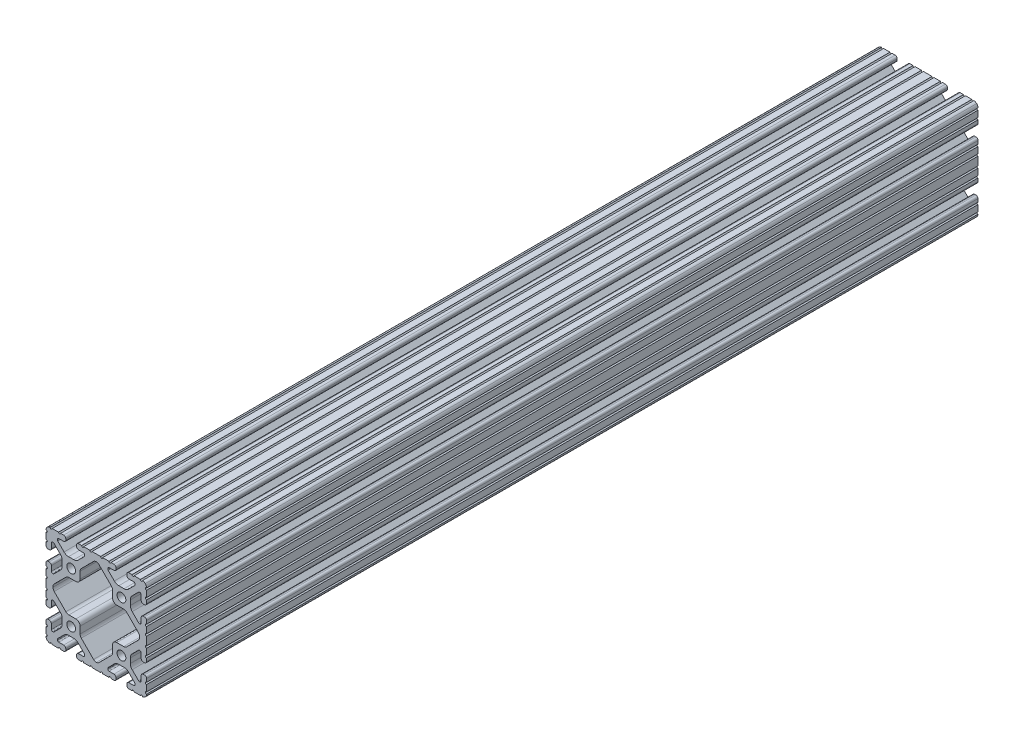
SolidWorks part; units mm, degrees
ref_plane "Front Plane" through (0, 0, 0) normal (0, 0, 1) x (1, 0, 0)
ref_plane "Top Plane" through (0, 0, 0) normal (0, 1, 0) x (1, 0, 0)
ref_plane "Right Plane" through (0, 0, 0) normal (1, 0, 0) x (0, 0, -1)
sketch "Sketch1" plane through (0, 0, 0) normal (0, 0, 1) x (1, 0, 0)
  line L0 (0, 38.1) -> (0, -38.1) construction
  line L1 (-38.1, -38.1) -> (38.1, -38.1) construction
  line L2 (-38.1, -38.1) -> (-38.1, 38.1) construction
  line L3 (-38.1, 38.1) -> (38.1, 38.1) construction
  line L4 (38.1, -38.1) -> (38.1, 38.1) construction
  line L5 (0, 38.1) -> (0, -38.1) construction
  line L6 (-38.1, 0) -> (38.1, 0) construction
  line L7 (-19.05, 19.05) -> (19.05, 19.05) construction
  line L8 (-19.05, 19.05) -> (-19.05, -19.05) construction
  line L9 (-19.05, -19.05) -> (19.05, -19.05) construction
  line L10 (19.05, 19.05) -> (19.05, -19.05) construction
  line L11 (-23.114, 38.1) -> (-23.114, -38.1) construction
  line L12 (-23.114, -38.1) -> (-14.986, 38.1) construction
  line L13 (-14.986, 38.1) -> (-14.986, -38.1) construction
  circle A0 centre (19.05, 19.05) radius 3.3274
  point P0 (0, 0)
  point P9 (0, 0)
  point P12 (-19.05, 0)
  line B0 (-11.3637, -22.8433) -> (-2.0515, -32.1555)
  line B1 (-12.2936, -15.4686) -> (-12.2936, -20.5983)
  line B2 (-20.769, -12.2936) -> (-15.4686, -12.2936)
  line B3 (-31.9021, -2.4756) -> (-23.0141, -11.3637)
  line B4 (-23.0141, 11.3637) -> (-31.9021, 2.4756)
  line B5 (-15.4686, 12.2936) -> (-20.769, 12.2936)
  line B6 (-12.2936, 20.5983) -> (-12.2936, 15.4686)
  line B7 (-2.0515, 32.1555) -> (-11.3637, 22.8433)
  line B8 (11.3637, 22.8433) -> (2.0515, 32.1555)
  line B9 (12.2936, 15.4686) -> (12.2936, 20.5983)
  line B10 (20.769, 12.2936) -> (15.4686, 12.2936)
  line B11 (31.9021, 2.4756) -> (23.0141, 11.3637)
  line B12 (23.0141, -11.3637) -> (31.9021, -2.4756)
  line B13 (15.4686, -12.2936) -> (20.769, -12.2936)
  line B14 (12.2936, -20.5983) -> (12.2936, -15.4686)
  line B15 (2.0515, -32.1555) -> (11.3637, -22.8433)
  line B16 (-4.7773, 38.1) -> (-9.6053, 38.1)
  line B17 (-11.1289, 38.1) -> (-13.4112, 38.1)
  line B18 (-14.986, 36.5252) -> (-14.986, 35.6108)
  line B19 (-13.4112, 34.036) -> (-9.652, 34.036)
  line B20 (-8.763, 33.147) -> (-8.763, 32.4935)
  line B21 (-9.0234, 31.8649) -> (-13.6907, 27.1976)
  line B22 (-17.0493, 25.8064) -> (-21.0507, 25.8064)
  line B23 (-24.4093, 27.1976) -> (-29.1002, 31.8885)
  line B24 (-29.337, 32.7207) -> (-29.337, 33.147)
  line B25 (-28.448, 34.036) -> (-24.6888, 34.036)
  line B26 (-23.114, 35.6108) -> (-23.114, 36.5252)
  line B27 (-24.6888, 38.1) -> (-27.0772, 38.1)
  line B28 (-28.6011, 38.1) -> (-33.4288, 38.1)
  line B29 (-38.1, 33.373) -> (-38.1, 28.5453)
  line B30 (-38.1, 27.0238) -> (-38.1, 24.6302)
  line B31 (-36.5252, 23.0554) -> (-35.6108, 23.0554)
  line B32 (-34.036, 24.6302) -> (-34.036, 28.448)
  line B33 (-33.147, 29.337) -> (-32.6643, 29.337)
  line B34 (-32.0357, 29.0766) -> (-27.1976, 24.2385)
  line B35 (-25.8064, 20.8799) -> (-25.8064, 17.2201)
  line B36 (-27.1976, 13.8615) -> (-31.9489, 9.1101)
  line B37 (-32.7869, 8.763) -> (-33.0603, 8.763)
  line B38 (-34.036, 9.7387) -> (-34.036, 13.4698)
  line B39 (-35.6108, 15.0446) -> (-36.5252, 15.0446)
  line B40 (-38.1, 13.4698) -> (-38.1, 11.075)
  line B41 (-38.1, 9.552) -> (-38.1, 4.7238)
  line B42 (-38.1, 3.2007) -> (-38.1, -3.2007)
  line B43 (-38.1, -4.7238) -> (-38.1, -9.552)
  line B44 (-38.1, -11.075) -> (-38.1, -13.4698)
  line B45 (-36.5252, -15.0446) -> (-35.6108, -15.0446)
  line B46 (-34.036, -13.4698) -> (-34.036, -9.7387)
  line B47 (-33.0603, -8.763) -> (-32.7869, -8.763)
  line B48 (-31.9489, -9.1101) -> (-27.1976, -13.8615)
  line B49 (-25.8064, -17.2201) -> (-25.8064, -20.8799)
  line B50 (-27.1976, -24.2385) -> (-32.0357, -29.0766)
  line B51 (-32.6643, -29.337) -> (-33.147, -29.337)
  line B52 (-34.036, -28.448) -> (-34.036, -24.6302)
  line B53 (-35.6108, -23.0554) -> (-36.5252, -23.0554)
  line B54 (-38.1, -24.6302) -> (-38.1, -27.0238)
  line B55 (-38.1, -28.5453) -> (-38.1, -33.373)
  line B56 (-33.4288, -38.1) -> (-28.6011, -38.1)
  line B57 (-27.0772, -38.1) -> (-24.6888, -38.1)
  line B58 (-23.114, -36.5252) -> (-23.114, -35.6108)
  line B59 (-24.6888, -34.036) -> (-28.448, -34.036)
  line B60 (-29.337, -33.147) -> (-29.337, -32.7207)
  line B61 (-29.1002, -31.8885) -> (-24.4093, -27.1976)
  line B62 (-21.0507, -25.8064) -> (-17.0493, -25.8064)
  line B63 (-13.6907, -27.1976) -> (-9.0234, -31.8649)
  line B64 (-8.763, -32.4935) -> (-8.763, -33.147)
  line B65 (-9.652, -34.036) -> (-13.4112, -34.036)
  line B66 (-14.986, -35.6108) -> (-14.986, -36.5252)
  line B67 (-13.4112, -38.1) -> (-11.1289, -38.1)
  line B68 (-9.6053, -38.1) -> (-4.7773, -38.1)
  line B69 (-3.2537, -38.1) -> (3.2537, -38.1)
  line B70 (4.7773, -38.1) -> (9.6053, -38.1)
  line B71 (11.1289, -38.1) -> (13.4112, -38.1)
  line B72 (14.986, -36.5252) -> (14.986, -35.6108)
  line B73 (13.4112, -34.036) -> (9.652, -34.036)
  line B74 (8.763, -33.147) -> (8.763, -32.4935)
  line B75 (9.0234, -31.8649) -> (13.6907, -27.1976)
  line B76 (17.0493, -25.8064) -> (21.0507, -25.8064)
  line B77 (24.4093, -27.1976) -> (29.1002, -31.8885)
  line B78 (29.337, -32.7207) -> (29.337, -33.147)
  line B79 (28.448, -34.036) -> (24.6888, -34.036)
  line B80 (23.114, -35.6108) -> (23.114, -36.5252)
  line B81 (24.6888, -38.1) -> (27.0772, -38.1)
  line B82 (28.6011, -38.1) -> (33.4288, -38.1)
  line B83 (38.1, -33.373) -> (38.1, -28.5453)
  line B84 (38.1, -27.0238) -> (38.1, -24.6302)
  line B85 (36.5252, -23.0554) -> (35.6108, -23.0554)
  line B86 (34.036, -24.6302) -> (34.036, -28.448)
  line B87 (33.147, -29.337) -> (32.6643, -29.337)
  line B88 (32.0357, -29.0766) -> (27.1976, -24.2385)
  line B89 (25.8064, -20.8799) -> (25.8064, -17.2201)
  line B90 (27.1976, -13.8615) -> (31.9489, -9.1101)
  line B91 (32.7869, -8.763) -> (33.0603, -8.763)
  line B92 (34.036, -9.7387) -> (34.036, -13.4698)
  line B93 (35.6108, -15.0446) -> (36.5252, -15.0446)
  line B94 (38.1, -13.4698) -> (38.1, -11.075)
  line B95 (38.1, -9.552) -> (38.1, -4.7238)
  line B96 (38.1, -3.2007) -> (38.1, 3.2007)
  line B97 (38.1, 4.7238) -> (38.1, 9.552)
  line B98 (38.1, 11.075) -> (38.1, 13.4698)
  line B99 (36.5252, 15.0446) -> (35.6108, 15.0446)
  line B100 (34.036, 13.4698) -> (34.036, 9.7387)
  line B101 (33.0603, 8.763) -> (32.7869, 8.763)
  line B102 (31.9489, 9.1101) -> (27.1976, 13.8615)
  line B103 (25.8064, 17.2201) -> (25.8064, 20.8799)
  line B104 (27.1976, 24.2385) -> (32.0357, 29.0766)
  line B105 (32.6643, 29.337) -> (33.147, 29.337)
  line B106 (34.036, 28.448) -> (34.036, 24.6302)
  line B107 (35.6108, 23.0554) -> (36.5252, 23.0554)
  line B108 (38.1, 24.6302) -> (38.1, 27.0238)
  line B109 (38.1, 28.5453) -> (38.1, 33.373)
  line B110 (33.4288, 38.1) -> (28.6011, 38.1)
  line B111 (27.0772, 38.1) -> (24.6888, 38.1)
  line B112 (23.114, 36.5252) -> (23.114, 35.6108)
  line B113 (24.6888, 34.036) -> (28.448, 34.036)
  line B114 (29.337, 33.147) -> (29.337, 32.7207)
  line B115 (29.1002, 31.8885) -> (24.4093, 27.1976)
  line B116 (21.0507, 25.8064) -> (17.0493, 25.8064)
  line B117 (13.6907, 27.1976) -> (9.0234, 31.8649)
  line B118 (8.763, 32.4935) -> (8.763, 33.147)
  line B119 (9.652, 34.036) -> (13.4112, 34.036)
  line B120 (14.986, 35.6108) -> (14.986, 36.5252)
  line B121 (13.4112, 38.1) -> (11.1289, 38.1)
  line B122 (9.6053, 38.1) -> (4.7773, 38.1)
  line B123 (3.2537, 38.1) -> (-3.2537, 38.1)
  circle B124 centre (-19.05, 19.05) radius 3.3274
  circle B125 centre (-19.05, -19.05) radius 3.3274
  circle B126 centre (19.05, -19.05) radius 3.3274
  circle B127 centre (19.05, 19.05) radius 3.3274
  arc B128 (0, -33.011) -> (2.0515, -32.1555) centre (-0.0139, -30.09) ccw
  arc B129 (-2.0515, -32.1555) -> (0, -33.011) centre (0.0139, -30.09) ccw
  arc B130 (-12.2936, -20.5983) -> (-11.3637, -22.8433) centre (-9.1186, -20.5983) ccw
  arc B131 (-12.2936, -15.4686) -> (-15.4686, -12.2936) centre (-15.4686, -15.4686) ccw
  arc B132 (-23.0141, -11.3637) -> (-20.769, -12.2936) centre (-20.769, -9.1186) ccw
  arc B133 (-32.7287, 0) -> (-31.9021, -2.4756) centre (-29.8367, -0.4102) ccw
  arc B134 (-31.9021, 2.4756) -> (-32.7287, 0) centre (-29.8367, 0.4102) ccw
  arc B135 (-20.769, 12.2936) -> (-23.0141, 11.3637) centre (-20.769, 9.1186) ccw
  arc B136 (-15.4686, 12.2936) -> (-12.2936, 15.4686) centre (-15.4686, 15.4686) ccw
  arc B137 (-11.3637, 22.8433) -> (-12.2936, 20.5983) centre (-9.1186, 20.5983) ccw
  arc B138 (0, 33.011) -> (-2.0515, 32.1555) centre (0.0139, 30.09) ccw
  arc B139 (2.0515, 32.1555) -> (0, 33.011) centre (-0.0139, 30.09) ccw
  arc B140 (12.2936, 20.5983) -> (11.3637, 22.8433) centre (9.1186, 20.5983) ccw
  arc B141 (12.2936, 15.4686) -> (15.4686, 12.2936) centre (15.4686, 15.4686) ccw
  arc B142 (23.0141, 11.3637) -> (20.769, 12.2936) centre (20.769, 9.1186) ccw
  arc B143 (32.7287, 0) -> (31.9021, 2.4756) centre (29.8367, 0.4102) ccw
  arc B144 (31.9021, -2.4756) -> (32.7287, 0) centre (29.8367, -0.4102) ccw
  arc B145 (20.769, -12.2936) -> (23.0141, -11.3637) centre (20.769, -9.1186) ccw
  arc B146 (15.4686, -12.2936) -> (12.2936, -15.4686) centre (15.4686, -15.4686) ccw
  arc B147 (11.3637, -22.8433) -> (12.2936, -20.5983) centre (9.1186, -20.5983) ccw
  arc B148 (-4.7773, 38.1) -> (-3.2537, 38.1) centre (-4.0155, 38.0824) ccw
  arc B149 (-11.1289, 38.1) -> (-9.6053, 38.1) centre (-10.3671, 38.0824) ccw
  arc B150 (-13.4112, 38.1) -> (-14.986, 36.5252) centre (-13.4112, 36.5252) ccw
  arc B151 (-14.986, 35.6108) -> (-13.4112, 34.036) centre (-13.4112, 35.6108) ccw
  arc B152 (-8.763, 33.147) -> (-9.652, 34.036) centre (-9.652, 33.147) ccw
  arc B153 (-9.0234, 31.8649) -> (-8.763, 32.4935) centre (-9.652, 32.4935) ccw
  arc B154 (-17.0493, 25.8064) -> (-13.6907, 27.1976) centre (-17.0493, 30.5562) ccw
  arc B155 (-24.4093, 27.1976) -> (-21.0507, 25.8064) centre (-21.0507, 30.5562) ccw
  arc B156 (-29.337, 32.7207) -> (-29.1002, 31.8885) centre (-28.4716, 32.5172) ccw
  arc B157 (-28.448, 34.036) -> (-29.337, 33.147) centre (-28.448, 33.147) ccw
  arc B158 (-24.6888, 34.036) -> (-23.114, 35.6108) centre (-24.6888, 35.6108) ccw
  arc B159 (-23.114, 36.5252) -> (-24.6888, 38.1) centre (-24.6888, 36.5252) ccw
  arc B160 (-28.6011, 38.1) -> (-27.0772, 38.1) centre (-27.8392, 38.0824) ccw
  arc B161 (-34.9527, 38.1) -> (-33.4288, 38.1) centre (-34.1907, 38.0824) ccw
  arc B162 (-34.9527, 38.1) -> (-37.0861, 37.1826) centre (-34.8521, 34.9266) ccw
  arc B163 (-37.0861, 37.1826) -> (-38.1, 34.8455) centre (-34.925, 34.8566) ccw
  arc B164 (-38.1, 33.373) -> (-38.1, 34.8455) centre (-37.9035, 34.1092) ccw
  arc B165 (-38.1, 27.0238) -> (-38.1, 28.5453) centre (-37.9035, 27.7845) ccw
  arc B166 (-38.1, 24.6302) -> (-36.5252, 23.0554) centre (-36.5252, 24.6302) ccw
  arc B167 (-35.6108, 23.0554) -> (-34.036, 24.6302) centre (-35.6108, 24.6302) ccw
  arc B168 (-33.147, 29.337) -> (-34.036, 28.448) centre (-33.147, 28.448) ccw
  arc B169 (-32.0357, 29.0766) -> (-32.6643, 29.337) centre (-32.6643, 28.448) ccw
  arc B170 (-25.8064, 20.8799) -> (-27.1976, 24.2385) centre (-30.5562, 20.8799) ccw
  arc B171 (-27.1976, 13.8615) -> (-25.8064, 17.2201) centre (-30.5562, 17.2201) ccw
  arc B172 (-32.7869, 8.763) -> (-31.9489, 9.1101) centre (-32.7869, 9.9481) ccw
  arc B173 (-34.036, 9.7387) -> (-33.0603, 8.763) centre (-33.0603, 9.7387) ccw
  arc B174 (-34.036, 13.4698) -> (-35.6108, 15.0446) centre (-35.6108, 13.4698) ccw
  arc B175 (-36.5252, 15.0446) -> (-38.1, 13.4698) centre (-36.5252, 13.4698) ccw
  arc B176 (-38.1, 9.552) -> (-38.1, 11.075) centre (-37.9035, 10.3135) ccw
  arc B177 (-38.1, 3.2007) -> (-38.1, 4.7238) centre (-37.9035, 3.9622) ccw
  arc B178 (-38.1, -4.7238) -> (-38.1, -3.2007) centre (-37.9035, -3.9622) ccw
  arc B179 (-38.1, -11.075) -> (-38.1, -9.552) centre (-37.9035, -10.3135) ccw
  arc B180 (-38.1, -13.4698) -> (-36.5252, -15.0446) centre (-36.5252, -13.4698) ccw
  arc B181 (-35.6108, -15.0446) -> (-34.036, -13.4698) centre (-35.6108, -13.4698) ccw
  arc B182 (-33.0603, -8.763) -> (-34.036, -9.7387) centre (-33.0603, -9.7387) ccw
  arc B183 (-31.9489, -9.1101) -> (-32.7869, -8.763) centre (-32.7869, -9.9481) ccw
  arc B184 (-25.8064, -17.2201) -> (-27.1976, -13.8615) centre (-30.5562, -17.2201) ccw
  arc B185 (-27.1976, -24.2385) -> (-25.8064, -20.8799) centre (-30.5562, -20.8799) ccw
  arc B186 (-32.6643, -29.337) -> (-32.0357, -29.0766) centre (-32.6643, -28.448) ccw
  arc B187 (-34.036, -28.448) -> (-33.147, -29.337) centre (-33.147, -28.448) ccw
  arc B188 (-34.036, -24.6302) -> (-35.6108, -23.0554) centre (-35.6108, -24.6302) ccw
  arc B189 (-36.5252, -23.0554) -> (-38.1, -24.6302) centre (-36.5252, -24.6302) ccw
  arc B190 (-38.1, -28.5453) -> (-38.1, -27.0238) centre (-37.9035, -27.7845) ccw
  arc B191 (-38.1, -34.8455) -> (-38.1, -33.373) centre (-37.9035, -34.1092) ccw
  arc B192 (-38.1, -34.8455) -> (-37.0861, -37.1826) centre (-34.925, -34.8566) ccw
  arc B193 (-37.0861, -37.1826) -> (-34.9527, -38.1) centre (-34.8521, -34.9266) ccw
  arc B194 (-33.4288, -38.1) -> (-34.9527, -38.1) centre (-34.1907, -38.0824) ccw
  arc B195 (-27.0772, -38.1) -> (-28.6011, -38.1) centre (-27.8392, -38.0824) ccw
  arc B196 (-24.6888, -38.1) -> (-23.114, -36.5252) centre (-24.6888, -36.5252) ccw
  arc B197 (-23.114, -35.6108) -> (-24.6888, -34.036) centre (-24.6888, -35.6108) ccw
  arc B198 (-29.337, -33.147) -> (-28.448, -34.036) centre (-28.448, -33.147) ccw
  arc B199 (-29.1002, -31.8885) -> (-29.337, -32.7207) centre (-28.4716, -32.5172) ccw
  arc B200 (-21.0507, -25.8064) -> (-24.4093, -27.1976) centre (-21.0507, -30.5562) ccw
  arc B201 (-13.6907, -27.1976) -> (-17.0493, -25.8064) centre (-17.0493, -30.5562) ccw
  arc B202 (-8.763, -32.4935) -> (-9.0234, -31.8649) centre (-9.652, -32.4935) ccw
  arc B203 (-9.652, -34.036) -> (-8.763, -33.147) centre (-9.652, -33.147) ccw
  arc B204 (-13.4112, -34.036) -> (-14.986, -35.6108) centre (-13.4112, -35.6108) ccw
  arc B205 (-14.986, -36.5252) -> (-13.4112, -38.1) centre (-13.4112, -36.5252) ccw
  arc B206 (-9.6053, -38.1) -> (-11.1289, -38.1) centre (-10.3671, -38.0824) ccw
  arc B207 (-3.2537, -38.1) -> (-4.7773, -38.1) centre (-4.0155, -38.0824) ccw
  arc B208 (4.7773, -38.1) -> (3.2537, -38.1) centre (4.0155, -38.0824) ccw
  arc B209 (11.1289, -38.1) -> (9.6053, -38.1) centre (10.3671, -38.0824) ccw
  arc B210 (13.4112, -38.1) -> (14.986, -36.5252) centre (13.4112, -36.5252) ccw
  arc B211 (14.986, -35.6108) -> (13.4112, -34.036) centre (13.4112, -35.6108) ccw
  arc B212 (8.763, -33.147) -> (9.652, -34.036) centre (9.652, -33.147) ccw
  arc B213 (9.0234, -31.8649) -> (8.763, -32.4935) centre (9.652, -32.4935) ccw
  arc B214 (17.0493, -25.8064) -> (13.6907, -27.1976) centre (17.0493, -30.5562) ccw
  arc B215 (24.4093, -27.1976) -> (21.0507, -25.8064) centre (21.0507, -30.5562) ccw
  arc B216 (29.337, -32.7207) -> (29.1002, -31.8885) centre (28.4716, -32.5172) ccw
  arc B217 (28.448, -34.036) -> (29.337, -33.147) centre (28.448, -33.147) ccw
  arc B218 (24.6888, -34.036) -> (23.114, -35.6108) centre (24.6888, -35.6108) ccw
  arc B219 (23.114, -36.5252) -> (24.6888, -38.1) centre (24.6888, -36.5252) ccw
  arc B220 (28.6011, -38.1) -> (27.0772, -38.1) centre (27.8392, -38.0824) ccw
  arc B221 (34.9527, -38.1) -> (33.4288, -38.1) centre (34.1907, -38.0824) ccw
  arc B222 (34.9527, -38.1) -> (37.0861, -37.1826) centre (34.8521, -34.9266) ccw
  arc B223 (37.0861, -37.1826) -> (38.1, -34.8455) centre (34.925, -34.8566) ccw
  arc B224 (38.1, -33.373) -> (38.1, -34.8455) centre (37.9035, -34.1092) ccw
  arc B225 (38.1, -27.0238) -> (38.1, -28.5453) centre (37.9035, -27.7845) ccw
  arc B226 (38.1, -24.6302) -> (36.5252, -23.0554) centre (36.5252, -24.6302) ccw
  arc B227 (35.6108, -23.0554) -> (34.036, -24.6302) centre (35.6108, -24.6302) ccw
  arc B228 (33.147, -29.337) -> (34.036, -28.448) centre (33.147, -28.448) ccw
  arc B229 (32.0357, -29.0766) -> (32.6643, -29.337) centre (32.6643, -28.448) ccw
  arc B230 (25.8064, -20.8799) -> (27.1976, -24.2385) centre (30.5562, -20.8799) ccw
  arc B231 (27.1976, -13.8615) -> (25.8064, -17.2201) centre (30.5562, -17.2201) ccw
  arc B232 (32.7869, -8.763) -> (31.9489, -9.1101) centre (32.7869, -9.9481) ccw
  arc B233 (34.036, -9.7387) -> (33.0603, -8.763) centre (33.0603, -9.7387) ccw
  arc B234 (34.036, -13.4698) -> (35.6108, -15.0446) centre (35.6108, -13.4698) ccw
  arc B235 (36.5252, -15.0446) -> (38.1, -13.4698) centre (36.5252, -13.4698) ccw
  arc B236 (38.1, -9.552) -> (38.1, -11.075) centre (37.9035, -10.3135) ccw
  arc B237 (38.1, -3.2007) -> (38.1, -4.7238) centre (37.9035, -3.9622) ccw
  arc B238 (38.1, 4.7238) -> (38.1, 3.2007) centre (37.9035, 3.9622) ccw
  arc B239 (38.1, 11.075) -> (38.1, 9.552) centre (37.9035, 10.3135) ccw
  arc B240 (38.1, 13.4698) -> (36.5252, 15.0446) centre (36.5252, 13.4698) ccw
  arc B241 (35.6108, 15.0446) -> (34.036, 13.4698) centre (35.6108, 13.4698) ccw
  arc B242 (33.0603, 8.763) -> (34.036, 9.7387) centre (33.0603, 9.7387) ccw
  arc B243 (31.9489, 9.1101) -> (32.7869, 8.763) centre (32.7869, 9.9481) ccw
  arc B244 (25.8064, 17.2201) -> (27.1976, 13.8615) centre (30.5562, 17.2201) ccw
  arc B245 (27.1976, 24.2385) -> (25.8064, 20.8799) centre (30.5562, 20.8799) ccw
  arc B246 (32.6643, 29.337) -> (32.0357, 29.0766) centre (32.6643, 28.448) ccw
  arc B247 (34.036, 28.448) -> (33.147, 29.337) centre (33.147, 28.448) ccw
  arc B248 (34.036, 24.6302) -> (35.6108, 23.0554) centre (35.6108, 24.6302) ccw
  arc B249 (36.5252, 23.0554) -> (38.1, 24.6302) centre (36.5252, 24.6302) ccw
  arc B250 (38.1, 28.5453) -> (38.1, 27.0238) centre (37.9035, 27.7845) ccw
  arc B251 (38.1, 34.8455) -> (38.1, 33.373) centre (37.9035, 34.1092) ccw
  arc B252 (38.1, 34.8455) -> (37.0861, 37.1826) centre (34.925, 34.8566) ccw
  arc B253 (37.0861, 37.1826) -> (34.9527, 38.1) centre (34.8521, 34.9266) ccw
  arc B254 (33.4288, 38.1) -> (34.9527, 38.1) centre (34.1907, 38.0824) ccw
  arc B255 (27.0772, 38.1) -> (28.6011, 38.1) centre (27.8392, 38.0824) ccw
  arc B256 (24.6888, 38.1) -> (23.114, 36.5252) centre (24.6888, 36.5252) ccw
  arc B257 (23.114, 35.6108) -> (24.6888, 34.036) centre (24.6888, 35.6108) ccw
  arc B258 (29.337, 33.147) -> (28.448, 34.036) centre (28.448, 33.147) ccw
  arc B259 (29.1002, 31.8885) -> (29.337, 32.7207) centre (28.4716, 32.5172) ccw
  arc B260 (21.0507, 25.8064) -> (24.4093, 27.1976) centre (21.0507, 30.5562) ccw
  arc B261 (13.6907, 27.1976) -> (17.0493, 25.8064) centre (17.0493, 30.5562) ccw
  arc B262 (8.763, 32.4935) -> (9.0234, 31.8649) centre (9.652, 32.4935) ccw
  arc B263 (9.652, 34.036) -> (8.763, 33.147) centre (9.652, 33.147) ccw
  arc B264 (13.4112, 34.036) -> (14.986, 35.6108) centre (13.4112, 35.6108) ccw
  arc B265 (14.986, 36.5252) -> (13.4112, 38.1) centre (13.4112, 36.5252) ccw
  arc B266 (9.6053, 38.1) -> (11.1289, 38.1) centre (10.3671, 38.0824) ccw
  arc B267 (3.2537, 38.1) -> (4.7773, 38.1) centre (4.0155, 38.0824) ccw
  dimension "Center Hole Diameter" = 6.6548
  dimension "Rail Width" = 76.2
  dimension "Rail Height" = 76.2
  dimension "T-Slot Width" = 8.128
sketch_block_instance "Block1-1"
sketch_block "Block1"
sketch "Sketch2" plane through (0, 0, 0) normal (1, 0, 0) x (0, 0, -1)
  line L0 (-315, 0) -> (315, 0) construction
  line L1 (-315, 38.1) -> (-315, -38.1) construction
  line L2 (-315, -38.1) -> (315, -38.1) construction
  line L3 (315, -38.1) -> (315, 38.1) construction
  line L4 (-213.4, 0) -> (-213.4, 38.1) construction
  line L5 (-213.4, 38.1) -> (213.4, 38.1) construction
  line L6 (213.4, 38.1) -> (213.4, 0) construction
  point P5 (213.4, 0)
  point P10 (-213.4, 0)
  dimension "D1" = 101.6
  dimension "Length" = 630
  dimension "D2" = 101.6
sketch "Sketch3" plane through (0, 0, 0) normal (0, 0, 1) x (1, 0, 0)
  line L0 (-11.3637, -22.8433) -> (-2.0515, -32.1555) construction
  line L1 (-12.2936, -15.4686) -> (-12.2936, -20.5983) construction
  line L2 (-20.769, -12.2936) -> (-15.4686, -12.2936) construction
  line L3 (-31.9021, -2.4756) -> (-23.0141, -11.3637) construction
  line L4 (-23.0141, 11.3637) -> (-31.9021, 2.4756) construction
  line L5 (-15.4686, 12.2936) -> (-20.769, 12.2936) construction
  line L6 (-12.2936, 20.5983) -> (-12.2936, 15.4686) construction
  line L7 (-2.0515, 32.1555) -> (-11.3637, 22.8433) construction
  line L8 (11.3637, 22.8433) -> (2.0515, 32.1555) construction
  line L9 (12.2936, 15.4686) -> (12.2936, 20.5983) construction
  line L10 (20.769, 12.2936) -> (15.4686, 12.2936) construction
  line L11 (31.9021, 2.4756) -> (23.0141, 11.3637) construction
  line L12 (23.0141, -11.3637) -> (31.9021, -2.4756) construction
  line L13 (15.4686, -12.2936) -> (20.769, -12.2936) construction
  line L14 (12.2936, -20.5983) -> (12.2936, -15.4686) construction
  line L15 (2.0515, -32.1555) -> (11.3637, -22.8433) construction
  line L16 (34.036, 28.448) -> (34.036, 24.6302) construction
  line L17 (35.6108, 23.0554) -> (36.5252, 23.0554) construction
  line L18 (38.1, 24.6302) -> (38.1, 27.0238) construction
  line L19 (38.1, 28.5453) -> (38.1, 33.373) construction
  line L20 (33.4288, 38.1) -> (28.6011, 38.1) construction
  line L21 (27.0772, 38.1) -> (24.6888, 38.1) construction
  line L22 (23.114, 36.5252) -> (23.114, 35.6108) construction
  line L23 (24.6888, 34.036) -> (28.448, 34.036) construction
  line L24 (29.337, 33.147) -> (29.337, 32.7207) construction
  line L25 (29.1002, 31.8885) -> (24.4093, 27.1976) construction
  line L26 (21.0507, 25.8064) -> (17.0493, 25.8064) construction
  line L27 (13.6907, 27.1976) -> (9.0234, 31.8649) construction
  line L28 (8.763, 32.4935) -> (8.763, 33.147) construction
  line L29 (9.652, 34.036) -> (13.4112, 34.036) construction
  line L30 (14.986, 35.6108) -> (14.986, 36.5252) construction
  line L31 (13.4112, 38.1) -> (11.1289, 38.1) construction
  line L32 (9.6053, 38.1) -> (4.7773, 38.1) construction
  line L33 (3.2537, 38.1) -> (-3.2537, 38.1) construction
  line L34 (-4.7773, 38.1) -> (-9.6053, 38.1) construction
  line L35 (-11.1289, 38.1) -> (-13.4112, 38.1) construction
  line L36 (-14.986, 36.5252) -> (-14.986, 35.6108) construction
  line L37 (-13.4112, 34.036) -> (-9.652, 34.036) construction
  line L38 (-8.763, 33.147) -> (-8.763, 32.4935) construction
  line L39 (-9.0234, 31.8649) -> (-13.6907, 27.1976) construction
  line L40 (-17.0493, 25.8064) -> (-21.0507, 25.8064) construction
  line L41 (-24.4093, 27.1976) -> (-29.1002, 31.8885) construction
  line L42 (-29.337, 32.7207) -> (-29.337, 33.147) construction
  line L43 (-28.448, 34.036) -> (-24.6888, 34.036) construction
  line L44 (-23.114, 35.6108) -> (-23.114, 36.5252) construction
  line L45 (-24.6888, 38.1) -> (-27.0772, 38.1) construction
  line L46 (-28.6011, 38.1) -> (-33.4288, 38.1) construction
  line L47 (-38.1, 33.373) -> (-38.1, 28.5453) construction
  line L48 (-38.1, 27.0238) -> (-38.1, 24.6302) construction
  line L49 (-36.5252, 23.0554) -> (-35.6108, 23.0554) construction
  line L50 (-34.036, 24.6302) -> (-34.036, 28.448) construction
  line L51 (-33.147, 29.337) -> (-32.6643, 29.337) construction
  line L52 (-32.0357, 29.0766) -> (-27.1976, 24.2385) construction
  line L53 (-25.8064, 20.8799) -> (-25.8064, 17.2201) construction
  line L54 (-27.1976, 13.8615) -> (-31.9489, 9.1101) construction
  line L55 (-32.7869, 8.763) -> (-33.0603, 8.763) construction
  line L56 (-34.036, 9.7387) -> (-34.036, 13.4698) construction
  line L57 (-35.6108, 15.0446) -> (-36.5252, 15.0446) construction
  line L58 (-38.1, 13.4698) -> (-38.1, 11.075) construction
  line L59 (-38.1, 9.552) -> (-38.1, 4.7238) construction
  line L60 (-38.1, 3.2007) -> (-38.1, -3.2007) construction
  line L61 (-38.1, -4.7238) -> (-38.1, -9.552) construction
  line L62 (-38.1, -11.075) -> (-38.1, -13.4698) construction
  line L63 (-36.5252, -15.0446) -> (-35.6108, -15.0446) construction
  line L64 (-34.036, -13.4698) -> (-34.036, -9.7387) construction
  line L65 (-33.0603, -8.763) -> (-32.7869, -8.763) construction
  line L66 (-31.9489, -9.1101) -> (-27.1976, -13.8615) construction
  line L67 (-25.8064, -17.2201) -> (-25.8064, -20.8799) construction
  line L68 (-27.1976, -24.2385) -> (-32.0357, -29.0766) construction
  line L69 (-32.6643, -29.337) -> (-33.147, -29.337) construction
  line L70 (-34.036, -28.448) -> (-34.036, -24.6302) construction
  line L71 (-35.6108, -23.0554) -> (-36.5252, -23.0554) construction
  line L72 (-38.1, -24.6302) -> (-38.1, -27.0238) construction
  line L73 (-38.1, -28.5453) -> (-38.1, -33.373) construction
  line L74 (-33.4288, -38.1) -> (-28.6011, -38.1) construction
  line L75 (-27.0772, -38.1) -> (-24.6888, -38.1) construction
  line L76 (-23.114, -36.5252) -> (-23.114, -35.6108) construction
  line L77 (-24.6888, -34.036) -> (-28.448, -34.036) construction
  line L78 (-29.337, -33.147) -> (-29.337, -32.7207) construction
  line L79 (-29.1002, -31.8885) -> (-24.4093, -27.1976) construction
  line L80 (-21.0507, -25.8064) -> (-17.0493, -25.8064) construction
  line L81 (-13.6907, -27.1976) -> (-9.0234, -31.8649) construction
  line L82 (-8.763, -32.4935) -> (-8.763, -33.147) construction
  line L83 (-9.652, -34.036) -> (-13.4112, -34.036) construction
  line L84 (-14.986, -35.6108) -> (-14.986, -36.5252) construction
  line L85 (-13.4112, -38.1) -> (-11.1289, -38.1) construction
  line L86 (-9.6053, -38.1) -> (-4.7773, -38.1) construction
  line L87 (-3.2537, -38.1) -> (3.2537, -38.1) construction
  line L88 (4.7773, -38.1) -> (9.6053, -38.1) construction
  line L89 (11.1289, -38.1) -> (13.4112, -38.1) construction
  line L90 (14.986, -36.5252) -> (14.986, -35.6108) construction
  line L91 (13.4112, -34.036) -> (9.652, -34.036) construction
  line L92 (8.763, -33.147) -> (8.763, -32.4935) construction
  line L93 (9.0234, -31.8649) -> (13.6907, -27.1976) construction
  line L94 (17.0493, -25.8064) -> (21.0507, -25.8064) construction
  line L95 (24.4093, -27.1976) -> (29.1002, -31.8885) construction
  line L96 (29.337, -32.7207) -> (29.337, -33.147) construction
  line L97 (28.448, -34.036) -> (24.6888, -34.036) construction
  line L98 (23.114, -35.6108) -> (23.114, -36.5252) construction
  line L99 (24.6888, -38.1) -> (27.0772, -38.1) construction
  line L100 (28.6011, -38.1) -> (33.4288, -38.1) construction
  line L101 (38.1, -33.373) -> (38.1, -28.5453) construction
  line L102 (38.1, -27.0238) -> (38.1, -24.6302) construction
  line L103 (36.5252, -23.0554) -> (35.6108, -23.0554) construction
  line L104 (34.036, -24.6302) -> (34.036, -28.448) construction
  line L105 (33.147, -29.337) -> (32.6643, -29.337) construction
  line L106 (32.0357, -29.0766) -> (27.1976, -24.2385) construction
  line L107 (25.8064, -20.8799) -> (25.8064, -17.2201) construction
  line L108 (27.1976, -13.8615) -> (31.9489, -9.1101) construction
  line L109 (32.7869, -8.763) -> (33.0603, -8.763) construction
  line L110 (34.036, -9.7387) -> (34.036, -13.4698) construction
  line L111 (35.6108, -15.0446) -> (36.5252, -15.0446) construction
  line L112 (38.1, -13.4698) -> (38.1, -11.075) construction
  line L113 (38.1, -9.552) -> (38.1, -4.7238) construction
  line L114 (38.1, -3.2007) -> (38.1, 3.2007) construction
  line L115 (38.1, 4.7238) -> (38.1, 9.552) construction
  line L116 (38.1, 11.075) -> (38.1, 13.4698) construction
  line L117 (36.5252, 15.0446) -> (35.6108, 15.0446) construction
  line L118 (34.036, 13.4698) -> (34.036, 9.7387) construction
  line L119 (33.0603, 8.763) -> (32.7869, 8.763) construction
  line L120 (31.9489, 9.1101) -> (27.1976, 13.8615) construction
  line L121 (25.8064, 17.2201) -> (25.8064, 20.8799) construction
  line L122 (27.1976, 24.2385) -> (32.0357, 29.0766) construction
  line L123 (32.6643, 29.337) -> (33.147, 29.337) construction
  line L124 (-11.3637, -22.8433) -> (-2.0515, -32.1555)
  line L125 (-12.2936, -15.4686) -> (-12.2936, -20.5983)
  line L126 (-20.769, -12.2936) -> (-15.4686, -12.2936)
  line L127 (-31.9021, -2.4756) -> (-23.0141, -11.3637)
  line L128 (-23.0141, 11.3637) -> (-31.9021, 2.4756)
  line L129 (-15.4686, 12.2936) -> (-20.769, 12.2936)
  line L130 (-12.2936, 20.5983) -> (-12.2936, 15.4686)
  line L131 (-2.0515, 32.1555) -> (-11.3637, 22.8433)
  line L132 (11.3637, 22.8433) -> (2.0515, 32.1555)
  line L133 (12.2936, 15.4686) -> (12.2936, 20.5983)
  line L134 (20.769, 12.2936) -> (15.4686, 12.2936)
  line L135 (31.9021, 2.4756) -> (23.0141, 11.3637)
  line L136 (23.0141, -11.3637) -> (31.9021, -2.4756)
  line L137 (15.4686, -12.2936) -> (20.769, -12.2936)
  line L138 (12.2936, -20.5983) -> (12.2936, -15.4686)
  line L139 (2.0515, -32.1555) -> (11.3637, -22.8433)
  line L140 (34.036, 28.448) -> (34.036, 24.6302)
  line L141 (35.6108, 23.0554) -> (36.5252, 23.0554)
  line L142 (38.1, 24.6302) -> (38.1, 27.0238)
  line L143 (38.1, 28.5453) -> (38.1, 33.373)
  line L144 (33.4288, 38.1) -> (28.6011, 38.1)
  line L145 (27.0772, 38.1) -> (24.6888, 38.1)
  line L146 (23.114, 36.5252) -> (23.114, 35.6108)
  line L147 (24.6888, 34.036) -> (28.448, 34.036)
  line L148 (29.337, 33.147) -> (29.337, 32.7207)
  line L149 (29.1002, 31.8885) -> (24.4093, 27.1976)
  line L150 (21.0507, 25.8064) -> (17.0493, 25.8064)
  line L151 (13.6907, 27.1976) -> (9.0234, 31.8649)
  line L152 (8.763, 32.4935) -> (8.763, 33.147)
  line L153 (9.652, 34.036) -> (13.4112, 34.036)
  line L154 (14.986, 35.6108) -> (14.986, 36.5252)
  line L155 (13.4112, 38.1) -> (11.1289, 38.1)
  line L156 (9.6053, 38.1) -> (4.7773, 38.1)
  line L157 (3.2537, 38.1) -> (-3.2537, 38.1)
  line L158 (-4.7773, 38.1) -> (-9.6053, 38.1)
  line L159 (-11.1289, 38.1) -> (-13.4112, 38.1)
  line L160 (-14.986, 36.5252) -> (-14.986, 35.6108)
  line L161 (-13.4112, 34.036) -> (-9.652, 34.036)
  line L162 (-8.763, 33.147) -> (-8.763, 32.4935)
  line L163 (-9.0234, 31.8649) -> (-13.6907, 27.1976)
  line L164 (-17.0493, 25.8064) -> (-21.0507, 25.8064)
  line L165 (-24.4093, 27.1976) -> (-29.1002, 31.8885)
  line L166 (-29.337, 32.7207) -> (-29.337, 33.147)
  line L167 (-28.448, 34.036) -> (-24.6888, 34.036)
  line L168 (-23.114, 35.6108) -> (-23.114, 36.5252)
  line L169 (-24.6888, 38.1) -> (-27.0772, 38.1)
  line L170 (-28.6011, 38.1) -> (-33.4288, 38.1)
  line L171 (-38.1, 33.373) -> (-38.1, 28.5453)
  line L172 (-38.1, 27.0238) -> (-38.1, 24.6302)
  line L173 (-36.5252, 23.0554) -> (-35.6108, 23.0554)
  line L174 (-34.036, 24.6302) -> (-34.036, 28.448)
  line L175 (-33.147, 29.337) -> (-32.6643, 29.337)
  line L176 (-32.0357, 29.0766) -> (-27.1976, 24.2385)
  line L177 (-25.8064, 20.8799) -> (-25.8064, 17.2201)
  line L178 (-27.1976, 13.8615) -> (-31.9489, 9.1101)
  line L179 (-32.7869, 8.763) -> (-33.0603, 8.763)
  line L180 (-34.036, 9.7387) -> (-34.036, 13.4698)
  line L181 (-35.6108, 15.0446) -> (-36.5252, 15.0446)
  line L182 (-38.1, 13.4698) -> (-38.1, 11.075)
  line L183 (-38.1, 9.552) -> (-38.1, 4.7238)
  line L184 (-38.1, 3.2007) -> (-38.1, -3.2007)
  line L185 (-38.1, -4.7238) -> (-38.1, -9.552)
  line L186 (-38.1, -11.075) -> (-38.1, -13.4698)
  line L187 (-36.5252, -15.0446) -> (-35.6108, -15.0446)
  line L188 (-34.036, -13.4698) -> (-34.036, -9.7387)
  line L189 (-33.0603, -8.763) -> (-32.7869, -8.763)
  line L190 (-31.9489, -9.1101) -> (-27.1976, -13.8615)
  line L191 (-25.8064, -17.2201) -> (-25.8064, -20.8799)
  line L192 (-27.1976, -24.2385) -> (-32.0357, -29.0766)
  line L193 (-32.6643, -29.337) -> (-33.147, -29.337)
  line L194 (-34.036, -28.448) -> (-34.036, -24.6302)
  line L195 (-35.6108, -23.0554) -> (-36.5252, -23.0554)
  line L196 (-38.1, -24.6302) -> (-38.1, -27.0238)
  line L197 (-38.1, -28.5453) -> (-38.1, -33.373)
  line L198 (-33.4288, -38.1) -> (-28.6011, -38.1)
  line L199 (-27.0772, -38.1) -> (-24.6888, -38.1)
  line L200 (-23.114, -36.5252) -> (-23.114, -35.6108)
  line L201 (-24.6888, -34.036) -> (-28.448, -34.036)
  line L202 (-29.337, -33.147) -> (-29.337, -32.7207)
  line L203 (-29.1002, -31.8885) -> (-24.4093, -27.1976)
  line L204 (-21.0507, -25.8064) -> (-17.0493, -25.8064)
  line L205 (-13.6907, -27.1976) -> (-9.0234, -31.8649)
  line L206 (-8.763, -32.4935) -> (-8.763, -33.147)
  line L207 (-9.652, -34.036) -> (-13.4112, -34.036)
  line L208 (-14.986, -35.6108) -> (-14.986, -36.5252)
  line L209 (-13.4112, -38.1) -> (-11.1289, -38.1)
  line L210 (-9.6053, -38.1) -> (-4.7773, -38.1)
  line L211 (-3.2537, -38.1) -> (3.2537, -38.1)
  line L212 (4.7773, -38.1) -> (9.6053, -38.1)
  line L213 (11.1289, -38.1) -> (13.4112, -38.1)
  line L214 (14.986, -36.5252) -> (14.986, -35.6108)
  line L215 (13.4112, -34.036) -> (9.652, -34.036)
  line L216 (8.763, -33.147) -> (8.763, -32.4935)
  line L217 (9.0234, -31.8649) -> (13.6907, -27.1976)
  line L218 (17.0493, -25.8064) -> (21.0507, -25.8064)
  line L219 (24.4093, -27.1976) -> (29.1002, -31.8885)
  line L220 (29.337, -32.7207) -> (29.337, -33.147)
  line L221 (28.448, -34.036) -> (24.6888, -34.036)
  line L222 (23.114, -35.6108) -> (23.114, -36.5252)
  line L223 (24.6888, -38.1) -> (27.0772, -38.1)
  line L224 (28.6011, -38.1) -> (33.4288, -38.1)
  line L225 (38.1, -33.373) -> (38.1, -28.5453)
  line L226 (38.1, -27.0238) -> (38.1, -24.6302)
  line L227 (36.5252, -23.0554) -> (35.6108, -23.0554)
  line L228 (34.036, -24.6302) -> (34.036, -28.448)
  line L229 (33.147, -29.337) -> (32.6643, -29.337)
  line L230 (32.0357, -29.0766) -> (27.1976, -24.2385)
  line L231 (25.8064, -20.8799) -> (25.8064, -17.2201)
  line L232 (27.1976, -13.8615) -> (31.9489, -9.1101)
  line L233 (32.7869, -8.763) -> (33.0603, -8.763)
  line L234 (34.036, -9.7387) -> (34.036, -13.4698)
  line L235 (35.6108, -15.0446) -> (36.5252, -15.0446)
  line L236 (38.1, -13.4698) -> (38.1, -11.075)
  line L237 (38.1, -9.552) -> (38.1, -4.7238)
  line L238 (38.1, -3.2007) -> (38.1, 3.2007)
  line L239 (38.1, 4.7238) -> (38.1, 9.552)
  line L240 (38.1, 11.075) -> (38.1, 13.4698)
  line L241 (36.5252, 15.0446) -> (35.6108, 15.0446)
  line L242 (34.036, 13.4698) -> (34.036, 9.7387)
  line L243 (33.0603, 8.763) -> (32.7869, 8.763)
  line L244 (31.9489, 9.1101) -> (27.1976, 13.8615)
  line L245 (25.8064, 17.2201) -> (25.8064, 20.8799)
  line L246 (27.1976, 24.2385) -> (32.0357, 29.0766)
  line L247 (32.6643, 29.337) -> (33.147, 29.337)
  arc A0 (-2.0515, -32.1555) -> (0, -33.011) centre (0.0139, -30.09) ccw construction
  circle A1 centre (19.05, 19.05) radius 3.3274
  circle A2 centre (19.05, 19.05) radius 3.3274
  arc A3 (-12.2936, -20.5983) -> (-11.3637, -22.8433) centre (-9.1186, -20.5983) ccw construction
  arc A4 (-12.2936, -15.4686) -> (-15.4686, -12.2936) centre (-15.4686, -15.4686) ccw construction
  arc A5 (-23.0141, -11.3637) -> (-20.769, -12.2936) centre (-20.769, -9.1186) ccw construction
  arc A6 (-32.7287, 0) -> (-31.9021, -2.4756) centre (-29.8367, -0.4102) ccw construction
  arc A7 (-31.9021, 2.4756) -> (-32.7287, 0) centre (-29.8367, 0.4102) ccw construction
  arc A8 (-20.769, 12.2936) -> (-23.0141, 11.3637) centre (-20.769, 9.1186) ccw construction
  arc A9 (-15.4686, 12.2936) -> (-12.2936, 15.4686) centre (-15.4686, 15.4686) ccw construction
  arc A10 (-11.3637, 22.8433) -> (-12.2936, 20.5983) centre (-9.1186, 20.5983) ccw construction
  arc A11 (0, 33.011) -> (-2.0515, 32.1555) centre (0.0139, 30.09) ccw construction
  arc A12 (2.0515, 32.1555) -> (0, 33.011) centre (-0.0139, 30.09) ccw construction
  arc A13 (12.2936, 20.5983) -> (11.3637, 22.8433) centre (9.1186, 20.5983) ccw construction
  arc A14 (12.2936, 15.4686) -> (15.4686, 12.2936) centre (15.4686, 15.4686) ccw construction
  arc A15 (23.0141, 11.3637) -> (20.769, 12.2936) centre (20.769, 9.1186) ccw construction
  arc A16 (32.7287, 0) -> (31.9021, 2.4756) centre (29.8367, 0.4102) ccw construction
  arc A17 (31.9021, -2.4756) -> (32.7287, 0) centre (29.8367, -0.4102) ccw construction
  arc A18 (20.769, -12.2936) -> (23.0141, -11.3637) centre (20.769, -9.1186) ccw construction
  arc A19 (15.4686, -12.2936) -> (12.2936, -15.4686) centre (15.4686, -15.4686) ccw construction
  arc A20 (11.3637, -22.8433) -> (12.2936, -20.5983) centre (9.1186, -20.5983) ccw construction
  arc A21 (0, -33.011) -> (2.0515, -32.1555) centre (-0.0139, -30.09) ccw construction
  circle A22 centre (-19.05, 19.05) radius 3.3274 construction
  circle A23 centre (19.05, -19.05) radius 3.3274 construction
  circle A24 centre (-19.05, -19.05) radius 3.3274 construction
  circle A25 centre (19.05, 19.05) radius 3.3274 construction
  arc A26 (34.036, 24.6302) -> (35.6108, 23.0554) centre (35.6108, 24.6302) ccw construction
  arc A27 (36.5252, 23.0554) -> (38.1, 24.6302) centre (36.5252, 24.6302) ccw construction
  arc A28 (38.1, 28.5453) -> (38.1, 27.0238) centre (37.9035, 27.7845) ccw construction
  arc A29 (38.1, 34.8455) -> (38.1, 33.373) centre (37.9035, 34.1092) ccw construction
  arc A30 (38.1, 34.8455) -> (37.0861, 37.1826) centre (34.925, 34.8566) ccw construction
  arc A31 (37.0861, 37.1826) -> (34.9527, 38.1) centre (34.8521, 34.9266) ccw construction
  arc A32 (33.4288, 38.1) -> (34.9527, 38.1) centre (34.1907, 38.0824) ccw construction
  arc A33 (27.0772, 38.1) -> (28.6011, 38.1) centre (27.8392, 38.0824) ccw construction
  arc A34 (24.6888, 38.1) -> (23.114, 36.5252) centre (24.6888, 36.5252) ccw construction
  arc A35 (23.114, 35.6108) -> (24.6888, 34.036) centre (24.6888, 35.6108) ccw construction
  arc A36 (29.337, 33.147) -> (28.448, 34.036) centre (28.448, 33.147) ccw construction
  arc A37 (29.1002, 31.8885) -> (29.337, 32.7207) centre (28.4716, 32.5172) ccw construction
  arc A38 (21.0507, 25.8064) -> (24.4093, 27.1976) centre (21.0507, 30.5562) ccw construction
  arc A39 (13.6907, 27.1976) -> (17.0493, 25.8064) centre (17.0493, 30.5562) ccw construction
  arc A40 (8.763, 32.4935) -> (9.0234, 31.8649) centre (9.652, 32.4935) ccw construction
  arc A41 (9.652, 34.036) -> (8.763, 33.147) centre (9.652, 33.147) ccw construction
  arc A42 (13.4112, 34.036) -> (14.986, 35.6108) centre (13.4112, 35.6108) ccw construction
  arc A43 (14.986, 36.5252) -> (13.4112, 38.1) centre (13.4112, 36.5252) ccw construction
  arc A44 (9.6053, 38.1) -> (11.1289, 38.1) centre (10.3671, 38.0824) ccw construction
  arc A45 (3.2537, 38.1) -> (4.7773, 38.1) centre (4.0155, 38.0824) ccw construction
  arc A46 (-4.7773, 38.1) -> (-3.2537, 38.1) centre (-4.0155, 38.0824) ccw construction
  arc A47 (-11.1289, 38.1) -> (-9.6053, 38.1) centre (-10.3671, 38.0824) ccw construction
  arc A48 (-13.4112, 38.1) -> (-14.986, 36.5252) centre (-13.4112, 36.5252) ccw construction
  arc A49 (-14.986, 35.6108) -> (-13.4112, 34.036) centre (-13.4112, 35.6108) ccw construction
  arc A50 (-8.763, 33.147) -> (-9.652, 34.036) centre (-9.652, 33.147) ccw construction
  arc A51 (-9.0234, 31.8649) -> (-8.763, 32.4935) centre (-9.652, 32.4935) ccw construction
  arc A52 (-17.0493, 25.8064) -> (-13.6907, 27.1976) centre (-17.0493, 30.5562) ccw construction
  arc A53 (-24.4093, 27.1976) -> (-21.0507, 25.8064) centre (-21.0507, 30.5562) ccw construction
  arc A54 (-29.337, 32.7207) -> (-29.1002, 31.8885) centre (-28.4716, 32.5172) ccw construction
  arc A55 (-28.448, 34.036) -> (-29.337, 33.147) centre (-28.448, 33.147) ccw construction
  arc A56 (-24.6888, 34.036) -> (-23.114, 35.6108) centre (-24.6888, 35.6108) ccw construction
  arc A57 (-23.114, 36.5252) -> (-24.6888, 38.1) centre (-24.6888, 36.5252) ccw construction
  arc A58 (-28.6011, 38.1) -> (-27.0772, 38.1) centre (-27.8392, 38.0824) ccw construction
  arc A59 (-34.9527, 38.1) -> (-33.4288, 38.1) centre (-34.1907, 38.0824) ccw construction
  arc A60 (-34.9527, 38.1) -> (-37.0861, 37.1826) centre (-34.8521, 34.9266) ccw construction
  arc A61 (-37.0861, 37.1826) -> (-38.1, 34.8455) centre (-34.925, 34.8566) ccw construction
  arc A62 (-38.1, 33.373) -> (-38.1, 34.8455) centre (-37.9035, 34.1092) ccw construction
  arc A63 (-38.1, 27.0238) -> (-38.1, 28.5453) centre (-37.9035, 27.7845) ccw construction
  arc A64 (-38.1, 24.6302) -> (-36.5252, 23.0554) centre (-36.5252, 24.6302) ccw construction
  arc A65 (-35.6108, 23.0554) -> (-34.036, 24.6302) centre (-35.6108, 24.6302) ccw construction
  arc A66 (-33.147, 29.337) -> (-34.036, 28.448) centre (-33.147, 28.448) ccw construction
  arc A67 (-32.0357, 29.0766) -> (-32.6643, 29.337) centre (-32.6643, 28.448) ccw construction
  arc A68 (-25.8064, 20.8799) -> (-27.1976, 24.2385) centre (-30.5562, 20.8799) ccw construction
  arc A69 (-27.1976, 13.8615) -> (-25.8064, 17.2201) centre (-30.5562, 17.2201) ccw construction
  arc A70 (-32.7869, 8.763) -> (-31.9489, 9.1101) centre (-32.7869, 9.9481) ccw construction
  arc A71 (-34.036, 9.7387) -> (-33.0603, 8.763) centre (-33.0603, 9.7387) ccw construction
  arc A72 (-34.036, 13.4698) -> (-35.6108, 15.0446) centre (-35.6108, 13.4698) ccw construction
  arc A73 (-36.5252, 15.0446) -> (-38.1, 13.4698) centre (-36.5252, 13.4698) ccw construction
  arc A74 (-38.1, 9.552) -> (-38.1, 11.075) centre (-37.9035, 10.3135) ccw construction
  arc A75 (-38.1, 3.2007) -> (-38.1, 4.7238) centre (-37.9035, 3.9622) ccw construction
  arc A76 (-38.1, -4.7238) -> (-38.1, -3.2007) centre (-37.9035, -3.9622) ccw construction
  arc A77 (-38.1, -11.075) -> (-38.1, -9.552) centre (-37.9035, -10.3135) ccw construction
  arc A78 (-38.1, -13.4698) -> (-36.5252, -15.0446) centre (-36.5252, -13.4698) ccw construction
  arc A79 (-35.6108, -15.0446) -> (-34.036, -13.4698) centre (-35.6108, -13.4698) ccw construction
  arc A80 (-33.0603, -8.763) -> (-34.036, -9.7387) centre (-33.0603, -9.7387) ccw construction
  arc A81 (-31.9489, -9.1101) -> (-32.7869, -8.763) centre (-32.7869, -9.9481) ccw construction
  arc A82 (-25.8064, -17.2201) -> (-27.1976, -13.8615) centre (-30.5562, -17.2201) ccw construction
  arc A83 (-27.1976, -24.2385) -> (-25.8064, -20.8799) centre (-30.5562, -20.8799) ccw construction
  arc A84 (-32.6643, -29.337) -> (-32.0357, -29.0766) centre (-32.6643, -28.448) ccw construction
  arc A85 (-34.036, -28.448) -> (-33.147, -29.337) centre (-33.147, -28.448) ccw construction
  arc A86 (-34.036, -24.6302) -> (-35.6108, -23.0554) centre (-35.6108, -24.6302) ccw construction
  arc A87 (-36.5252, -23.0554) -> (-38.1, -24.6302) centre (-36.5252, -24.6302) ccw construction
  arc A88 (-38.1, -28.5453) -> (-38.1, -27.0238) centre (-37.9035, -27.7845) ccw construction
  arc A89 (-38.1, -34.8455) -> (-38.1, -33.373) centre (-37.9035, -34.1092) ccw construction
  arc A90 (-38.1, -34.8455) -> (-37.0861, -37.1826) centre (-34.925, -34.8566) ccw construction
  arc A91 (-37.0861, -37.1826) -> (-34.9527, -38.1) centre (-34.8521, -34.9266) ccw construction
  arc A92 (-33.4288, -38.1) -> (-34.9527, -38.1) centre (-34.1907, -38.0824) ccw construction
  arc A93 (-27.0772, -38.1) -> (-28.6011, -38.1) centre (-27.8392, -38.0824) ccw construction
  arc A94 (-24.6888, -38.1) -> (-23.114, -36.5252) centre (-24.6888, -36.5252) ccw construction
  arc A95 (-23.114, -35.6108) -> (-24.6888, -34.036) centre (-24.6888, -35.6108) ccw construction
  arc A96 (-29.337, -33.147) -> (-28.448, -34.036) centre (-28.448, -33.147) ccw construction
  arc A97 (-29.1002, -31.8885) -> (-29.337, -32.7207) centre (-28.4716, -32.5172) ccw construction
  arc A98 (-21.0507, -25.8064) -> (-24.4093, -27.1976) centre (-21.0507, -30.5562) ccw construction
  arc A99 (-13.6907, -27.1976) -> (-17.0493, -25.8064) centre (-17.0493, -30.5562) ccw construction
  arc A100 (-8.763, -32.4935) -> (-9.0234, -31.8649) centre (-9.652, -32.4935) ccw construction
  arc A101 (-9.652, -34.036) -> (-8.763, -33.147) centre (-9.652, -33.147) ccw construction
  arc A102 (-13.4112, -34.036) -> (-14.986, -35.6108) centre (-13.4112, -35.6108) ccw construction
  arc A103 (-14.986, -36.5252) -> (-13.4112, -38.1) centre (-13.4112, -36.5252) ccw construction
  arc A104 (-9.6053, -38.1) -> (-11.1289, -38.1) centre (-10.3671, -38.0824) ccw construction
  arc A105 (-3.2537, -38.1) -> (-4.7773, -38.1) centre (-4.0155, -38.0824) ccw construction
  arc A106 (4.7773, -38.1) -> (3.2537, -38.1) centre (4.0155, -38.0824) ccw construction
  arc A107 (11.1289, -38.1) -> (9.6053, -38.1) centre (10.3671, -38.0824) ccw construction
  arc A108 (13.4112, -38.1) -> (14.986, -36.5252) centre (13.4112, -36.5252) ccw construction
  arc A109 (14.986, -35.6108) -> (13.4112, -34.036) centre (13.4112, -35.6108) ccw construction
  arc A110 (8.763, -33.147) -> (9.652, -34.036) centre (9.652, -33.147) ccw construction
  arc A111 (9.0234, -31.8649) -> (8.763, -32.4935) centre (9.652, -32.4935) ccw construction
  arc A112 (17.0493, -25.8064) -> (13.6907, -27.1976) centre (17.0493, -30.5562) ccw construction
  arc A113 (24.4093, -27.1976) -> (21.0507, -25.8064) centre (21.0507, -30.5562) ccw construction
  arc A114 (29.337, -32.7207) -> (29.1002, -31.8885) centre (28.4716, -32.5172) ccw construction
  arc A115 (28.448, -34.036) -> (29.337, -33.147) centre (28.448, -33.147) ccw construction
  arc A116 (24.6888, -34.036) -> (23.114, -35.6108) centre (24.6888, -35.6108) ccw construction
  arc A117 (23.114, -36.5252) -> (24.6888, -38.1) centre (24.6888, -36.5252) ccw construction
  arc A118 (28.6011, -38.1) -> (27.0772, -38.1) centre (27.8392, -38.0824) ccw construction
  arc A119 (34.9527, -38.1) -> (33.4288, -38.1) centre (34.1907, -38.0824) ccw construction
  arc A120 (34.9527, -38.1) -> (37.0861, -37.1826) centre (34.8521, -34.9266) ccw construction
  arc A121 (37.0861, -37.1826) -> (38.1, -34.8455) centre (34.925, -34.8566) ccw construction
  arc A122 (38.1, -33.373) -> (38.1, -34.8455) centre (37.9035, -34.1092) ccw construction
  arc A123 (38.1, -27.0238) -> (38.1, -28.5453) centre (37.9035, -27.7845) ccw construction
  arc A124 (38.1, -24.6302) -> (36.5252, -23.0554) centre (36.5252, -24.6302) ccw construction
  arc A125 (35.6108, -23.0554) -> (34.036, -24.6302) centre (35.6108, -24.6302) ccw construction
  arc A126 (33.147, -29.337) -> (34.036, -28.448) centre (33.147, -28.448) ccw construction
  arc A127 (32.0357, -29.0766) -> (32.6643, -29.337) centre (32.6643, -28.448) ccw construction
  arc A128 (25.8064, -20.8799) -> (27.1976, -24.2385) centre (30.5562, -20.8799) ccw construction
  arc A129 (27.1976, -13.8615) -> (25.8064, -17.2201) centre (30.5562, -17.2201) ccw construction
  arc A130 (32.7869, -8.763) -> (31.9489, -9.1101) centre (32.7869, -9.9481) ccw construction
  arc A131 (34.036, -9.7387) -> (33.0603, -8.763) centre (33.0603, -9.7387) ccw construction
  arc A132 (34.036, -13.4698) -> (35.6108, -15.0446) centre (35.6108, -13.4698) ccw construction
  arc A133 (36.5252, -15.0446) -> (38.1, -13.4698) centre (36.5252, -13.4698) ccw construction
  arc A134 (38.1, -9.552) -> (38.1, -11.075) centre (37.9035, -10.3135) ccw construction
  arc A135 (38.1, -3.2007) -> (38.1, -4.7238) centre (37.9035, -3.9622) ccw construction
  arc A136 (38.1, 4.7238) -> (38.1, 3.2007) centre (37.9035, 3.9622) ccw construction
  arc A137 (38.1, 11.075) -> (38.1, 9.552) centre (37.9035, 10.3135) ccw construction
  arc A138 (38.1, 13.4698) -> (36.5252, 15.0446) centre (36.5252, 13.4698) ccw construction
  arc A139 (35.6108, 15.0446) -> (34.036, 13.4698) centre (35.6108, 13.4698) ccw construction
  arc A140 (33.0603, 8.763) -> (34.036, 9.7387) centre (33.0603, 9.7387) ccw construction
  arc A141 (31.9489, 9.1101) -> (32.7869, 8.763) centre (32.7869, 9.9481) ccw construction
  arc A142 (25.8064, 17.2201) -> (27.1976, 13.8615) centre (30.5562, 17.2201) ccw construction
  arc A143 (27.1976, 24.2385) -> (25.8064, 20.8799) centre (30.5562, 20.8799) ccw construction
  arc A144 (32.6643, 29.337) -> (32.0357, 29.0766) centre (32.6643, 28.448) ccw construction
  arc A145 (34.036, 28.448) -> (33.147, 29.337) centre (33.147, 28.448) ccw construction
  arc A146 (-2.0515, -32.1555) -> (0, -33.011) centre (0.0139, -30.09) ccw
  arc A147 (-12.2936, -20.5983) -> (-11.3637, -22.8433) centre (-9.1186, -20.5983) ccw
  arc A148 (-12.2936, -15.4686) -> (-15.4686, -12.2936) centre (-15.4686, -15.4686) ccw
  arc A149 (-23.0141, -11.3637) -> (-20.769, -12.2936) centre (-20.769, -9.1186) ccw
  arc A150 (-32.7287, 0) -> (-31.9021, -2.4756) centre (-29.8367, -0.4102) ccw
  arc A151 (-31.9021, 2.4756) -> (-32.7287, 0) centre (-29.8367, 0.4102) ccw
  arc A152 (-20.769, 12.2936) -> (-23.0141, 11.3637) centre (-20.769, 9.1186) ccw
  arc A153 (-15.4686, 12.2936) -> (-12.2936, 15.4686) centre (-15.4686, 15.4686) ccw
  arc A154 (-11.3637, 22.8433) -> (-12.2936, 20.5983) centre (-9.1186, 20.5983) ccw
  arc A155 (0, 33.011) -> (-2.0515, 32.1555) centre (0.0139, 30.09) ccw
  arc A156 (2.0515, 32.1555) -> (0, 33.011) centre (-0.0139, 30.09) ccw
  arc A157 (12.2936, 20.5983) -> (11.3637, 22.8433) centre (9.1186, 20.5983) ccw
  arc A158 (12.2936, 15.4686) -> (15.4686, 12.2936) centre (15.4686, 15.4686) ccw
  arc A159 (23.0141, 11.3637) -> (20.769, 12.2936) centre (20.769, 9.1186) ccw
  arc A160 (32.7287, 0) -> (31.9021, 2.4756) centre (29.8367, 0.4102) ccw
  arc A161 (31.9021, -2.4756) -> (32.7287, 0) centre (29.8367, -0.4102) ccw
  arc A162 (20.769, -12.2936) -> (23.0141, -11.3637) centre (20.769, -9.1186) ccw
  arc A163 (15.4686, -12.2936) -> (12.2936, -15.4686) centre (15.4686, -15.4686) ccw
  arc A164 (11.3637, -22.8433) -> (12.2936, -20.5983) centre (9.1186, -20.5983) ccw
  arc A165 (0, -33.011) -> (2.0515, -32.1555) centre (-0.0139, -30.09) ccw
  circle A166 centre (-19.05, 19.05) radius 3.3274
  circle A167 centre (19.05, -19.05) radius 3.3274
  circle A168 centre (-19.05, -19.05) radius 3.3274
  circle A169 centre (19.05, 19.05) radius 3.3274
  arc A170 (34.036, 24.6302) -> (35.6108, 23.0554) centre (35.6108, 24.6302) ccw
  arc A171 (36.5252, 23.0554) -> (38.1, 24.6302) centre (36.5252, 24.6302) ccw
  arc A172 (38.1, 28.5453) -> (38.1, 27.0238) centre (37.9035, 27.7845) ccw
  arc A173 (38.1, 34.8455) -> (38.1, 33.373) centre (37.9035, 34.1092) ccw
  arc A174 (38.1, 34.8455) -> (37.0861, 37.1826) centre (34.925, 34.8566) ccw
  arc A175 (37.0861, 37.1826) -> (34.9527, 38.1) centre (34.8521, 34.9266) ccw
  arc A176 (33.4288, 38.1) -> (34.9527, 38.1) centre (34.1907, 38.0824) ccw
  arc A177 (27.0772, 38.1) -> (28.6011, 38.1) centre (27.8392, 38.0824) ccw
  arc A178 (24.6888, 38.1) -> (23.114, 36.5252) centre (24.6888, 36.5252) ccw
  arc A179 (23.114, 35.6108) -> (24.6888, 34.036) centre (24.6888, 35.6108) ccw
  arc A180 (29.337, 33.147) -> (28.448, 34.036) centre (28.448, 33.147) ccw
  arc A181 (29.1002, 31.8885) -> (29.337, 32.7207) centre (28.4716, 32.5172) ccw
  arc A182 (21.0507, 25.8064) -> (24.4093, 27.1976) centre (21.0507, 30.5562) ccw
  arc A183 (13.6907, 27.1976) -> (17.0493, 25.8064) centre (17.0493, 30.5562) ccw
  arc A184 (8.763, 32.4935) -> (9.0234, 31.8649) centre (9.652, 32.4935) ccw
  arc A185 (9.652, 34.036) -> (8.763, 33.147) centre (9.652, 33.147) ccw
  arc A186 (13.4112, 34.036) -> (14.986, 35.6108) centre (13.4112, 35.6108) ccw
  arc A187 (14.986, 36.5252) -> (13.4112, 38.1) centre (13.4112, 36.5252) ccw
  arc A188 (9.6053, 38.1) -> (11.1289, 38.1) centre (10.3671, 38.0824) ccw
  arc A189 (3.2537, 38.1) -> (4.7773, 38.1) centre (4.0155, 38.0824) ccw
  arc A190 (-4.7773, 38.1) -> (-3.2537, 38.1) centre (-4.0155, 38.0824) ccw
  arc A191 (-11.1289, 38.1) -> (-9.6053, 38.1) centre (-10.3671, 38.0824) ccw
  arc A192 (-13.4112, 38.1) -> (-14.986, 36.5252) centre (-13.4112, 36.5252) ccw
  arc A193 (-14.986, 35.6108) -> (-13.4112, 34.036) centre (-13.4112, 35.6108) ccw
  arc A194 (-8.763, 33.147) -> (-9.652, 34.036) centre (-9.652, 33.147) ccw
  arc A195 (-9.0234, 31.8649) -> (-8.763, 32.4935) centre (-9.652, 32.4935) ccw
  arc A196 (-17.0493, 25.8064) -> (-13.6907, 27.1976) centre (-17.0493, 30.5562) ccw
  arc A197 (-24.4093, 27.1976) -> (-21.0507, 25.8064) centre (-21.0507, 30.5562) ccw
  arc A198 (-29.337, 32.7207) -> (-29.1002, 31.8885) centre (-28.4716, 32.5172) ccw
  arc A199 (-28.448, 34.036) -> (-29.337, 33.147) centre (-28.448, 33.147) ccw
  arc A200 (-24.6888, 34.036) -> (-23.114, 35.6108) centre (-24.6888, 35.6108) ccw
  arc A201 (-23.114, 36.5252) -> (-24.6888, 38.1) centre (-24.6888, 36.5252) ccw
  arc A202 (-28.6011, 38.1) -> (-27.0772, 38.1) centre (-27.8392, 38.0824) ccw
  arc A203 (-34.9527, 38.1) -> (-33.4288, 38.1) centre (-34.1907, 38.0824) ccw
  arc A204 (-34.9527, 38.1) -> (-37.0861, 37.1826) centre (-34.8521, 34.9266) ccw
  arc A205 (-37.0861, 37.1826) -> (-38.1, 34.8455) centre (-34.925, 34.8566) ccw
  arc A206 (-38.1, 33.373) -> (-38.1, 34.8455) centre (-37.9035, 34.1092) ccw
  arc A207 (-38.1, 27.0238) -> (-38.1, 28.5453) centre (-37.9035, 27.7845) ccw
  arc A208 (-38.1, 24.6302) -> (-36.5252, 23.0554) centre (-36.5252, 24.6302) ccw
  arc A209 (-35.6108, 23.0554) -> (-34.036, 24.6302) centre (-35.6108, 24.6302) ccw
  arc A210 (-33.147, 29.337) -> (-34.036, 28.448) centre (-33.147, 28.448) ccw
  arc A211 (-32.0357, 29.0766) -> (-32.6643, 29.337) centre (-32.6643, 28.448) ccw
  arc A212 (-25.8064, 20.8799) -> (-27.1976, 24.2385) centre (-30.5562, 20.8799) ccw
  arc A213 (-27.1976, 13.8615) -> (-25.8064, 17.2201) centre (-30.5562, 17.2201) ccw
  arc A214 (-32.7869, 8.763) -> (-31.9489, 9.1101) centre (-32.7869, 9.9481) ccw
  arc A215 (-34.036, 9.7387) -> (-33.0603, 8.763) centre (-33.0603, 9.7387) ccw
  arc A216 (-34.036, 13.4698) -> (-35.6108, 15.0446) centre (-35.6108, 13.4698) ccw
  arc A217 (-36.5252, 15.0446) -> (-38.1, 13.4698) centre (-36.5252, 13.4698) ccw
  arc A218 (-38.1, 9.552) -> (-38.1, 11.075) centre (-37.9035, 10.3135) ccw
  arc A219 (-38.1, 3.2007) -> (-38.1, 4.7238) centre (-37.9035, 3.9622) ccw
  arc A220 (-38.1, -4.7238) -> (-38.1, -3.2007) centre (-37.9035, -3.9622) ccw
  arc A221 (-38.1, -11.075) -> (-38.1, -9.552) centre (-37.9035, -10.3135) ccw
  arc A222 (-38.1, -13.4698) -> (-36.5252, -15.0446) centre (-36.5252, -13.4698) ccw
  arc A223 (-35.6108, -15.0446) -> (-34.036, -13.4698) centre (-35.6108, -13.4698) ccw
  arc A224 (-33.0603, -8.763) -> (-34.036, -9.7387) centre (-33.0603, -9.7387) ccw
  arc A225 (-31.9489, -9.1101) -> (-32.7869, -8.763) centre (-32.7869, -9.9481) ccw
  arc A226 (-25.8064, -17.2201) -> (-27.1976, -13.8615) centre (-30.5562, -17.2201) ccw
  arc A227 (-27.1976, -24.2385) -> (-25.8064, -20.8799) centre (-30.5562, -20.8799) ccw
  arc A228 (-32.6643, -29.337) -> (-32.0357, -29.0766) centre (-32.6643, -28.448) ccw
  arc A229 (-34.036, -28.448) -> (-33.147, -29.337) centre (-33.147, -28.448) ccw
  arc A230 (-34.036, -24.6302) -> (-35.6108, -23.0554) centre (-35.6108, -24.6302) ccw
  arc A231 (-36.5252, -23.0554) -> (-38.1, -24.6302) centre (-36.5252, -24.6302) ccw
  arc A232 (-38.1, -28.5453) -> (-38.1, -27.0238) centre (-37.9035, -27.7845) ccw
  arc A233 (-38.1, -34.8455) -> (-38.1, -33.373) centre (-37.9035, -34.1092) ccw
  arc A234 (-38.1, -34.8455) -> (-37.0861, -37.1826) centre (-34.925, -34.8566) ccw
  arc A235 (-37.0861, -37.1826) -> (-34.9527, -38.1) centre (-34.8521, -34.9266) ccw
  arc A236 (-33.4288, -38.1) -> (-34.9527, -38.1) centre (-34.1907, -38.0824) ccw
  arc A237 (-27.0772, -38.1) -> (-28.6011, -38.1) centre (-27.8392, -38.0824) ccw
  arc A238 (-24.6888, -38.1) -> (-23.114, -36.5252) centre (-24.6888, -36.5252) ccw
  arc A239 (-23.114, -35.6108) -> (-24.6888, -34.036) centre (-24.6888, -35.6108) ccw
  arc A240 (-29.337, -33.147) -> (-28.448, -34.036) centre (-28.448, -33.147) ccw
  arc A241 (-29.1002, -31.8885) -> (-29.337, -32.7207) centre (-28.4716, -32.5172) ccw
  arc A242 (-21.0507, -25.8064) -> (-24.4093, -27.1976) centre (-21.0507, -30.5562) ccw
  arc A243 (-13.6907, -27.1976) -> (-17.0493, -25.8064) centre (-17.0493, -30.5562) ccw
  arc A244 (-8.763, -32.4935) -> (-9.0234, -31.8649) centre (-9.652, -32.4935) ccw
  arc A245 (-9.652, -34.036) -> (-8.763, -33.147) centre (-9.652, -33.147) ccw
  arc A246 (-13.4112, -34.036) -> (-14.986, -35.6108) centre (-13.4112, -35.6108) ccw
  arc A247 (-14.986, -36.5252) -> (-13.4112, -38.1) centre (-13.4112, -36.5252) ccw
  arc A248 (-9.6053, -38.1) -> (-11.1289, -38.1) centre (-10.3671, -38.0824) ccw
  arc A249 (-3.2537, -38.1) -> (-4.7773, -38.1) centre (-4.0155, -38.0824) ccw
  arc A250 (4.7773, -38.1) -> (3.2537, -38.1) centre (4.0155, -38.0824) ccw
  arc A251 (11.1289, -38.1) -> (9.6053, -38.1) centre (10.3671, -38.0824) ccw
  arc A252 (13.4112, -38.1) -> (14.986, -36.5252) centre (13.4112, -36.5252) ccw
  arc A253 (14.986, -35.6108) -> (13.4112, -34.036) centre (13.4112, -35.6108) ccw
  arc A254 (8.763, -33.147) -> (9.652, -34.036) centre (9.652, -33.147) ccw
  arc A255 (9.0234, -31.8649) -> (8.763, -32.4935) centre (9.652, -32.4935) ccw
  arc A256 (17.0493, -25.8064) -> (13.6907, -27.1976) centre (17.0493, -30.5562) ccw
  arc A257 (24.4093, -27.1976) -> (21.0507, -25.8064) centre (21.0507, -30.5562) ccw
  arc A258 (29.337, -32.7207) -> (29.1002, -31.8885) centre (28.4716, -32.5172) ccw
  arc A259 (28.448, -34.036) -> (29.337, -33.147) centre (28.448, -33.147) ccw
  arc A260 (24.6888, -34.036) -> (23.114, -35.6108) centre (24.6888, -35.6108) ccw
  arc A261 (23.114, -36.5252) -> (24.6888, -38.1) centre (24.6888, -36.5252) ccw
  arc A262 (28.6011, -38.1) -> (27.0772, -38.1) centre (27.8392, -38.0824) ccw
  arc A263 (34.9527, -38.1) -> (33.4288, -38.1) centre (34.1907, -38.0824) ccw
  arc A264 (34.9527, -38.1) -> (37.0861, -37.1826) centre (34.8521, -34.9266) ccw
  arc A265 (37.0861, -37.1826) -> (38.1, -34.8455) centre (34.925, -34.8566) ccw
  arc A266 (38.1, -33.373) -> (38.1, -34.8455) centre (37.9035, -34.1092) ccw
  arc A267 (38.1, -27.0238) -> (38.1, -28.5453) centre (37.9035, -27.7845) ccw
  arc A268 (38.1, -24.6302) -> (36.5252, -23.0554) centre (36.5252, -24.6302) ccw
  arc A269 (35.6108, -23.0554) -> (34.036, -24.6302) centre (35.6108, -24.6302) ccw
  arc A270 (33.147, -29.337) -> (34.036, -28.448) centre (33.147, -28.448) ccw
  arc A271 (32.0357, -29.0766) -> (32.6643, -29.337) centre (32.6643, -28.448) ccw
  arc A272 (25.8064, -20.8799) -> (27.1976, -24.2385) centre (30.5562, -20.8799) ccw
  arc A273 (27.1976, -13.8615) -> (25.8064, -17.2201) centre (30.5562, -17.2201) ccw
  arc A274 (32.7869, -8.763) -> (31.9489, -9.1101) centre (32.7869, -9.9481) ccw
  arc A275 (34.036, -9.7387) -> (33.0603, -8.763) centre (33.0603, -9.7387) ccw
  arc A276 (34.036, -13.4698) -> (35.6108, -15.0446) centre (35.6108, -13.4698) ccw
  arc A277 (36.5252, -15.0446) -> (38.1, -13.4698) centre (36.5252, -13.4698) ccw
  arc A278 (38.1, -9.552) -> (38.1, -11.075) centre (37.9035, -10.3135) ccw
  arc A279 (38.1, -3.2007) -> (38.1, -4.7238) centre (37.9035, -3.9622) ccw
  arc A280 (38.1, 4.7238) -> (38.1, 3.2007) centre (37.9035, 3.9622) ccw
  arc A281 (38.1, 11.075) -> (38.1, 9.552) centre (37.9035, 10.3135) ccw
  arc A282 (38.1, 13.4698) -> (36.5252, 15.0446) centre (36.5252, 13.4698) ccw
  arc A283 (35.6108, 15.0446) -> (34.036, 13.4698) centre (35.6108, 13.4698) ccw
  arc A284 (33.0603, 8.763) -> (34.036, 9.7387) centre (33.0603, 9.7387) ccw
  arc A285 (31.9489, 9.1101) -> (32.7869, 8.763) centre (32.7869, 9.9481) ccw
  arc A286 (25.8064, 17.2201) -> (27.1976, 13.8615) centre (30.5562, 17.2201) ccw
  arc A287 (27.1976, 24.2385) -> (25.8064, 20.8799) centre (30.5562, 20.8799) ccw
  arc A288 (32.6643, 29.337) -> (32.0357, 29.0766) centre (32.6643, 28.448) ccw
  arc A289 (34.036, 28.448) -> (33.147, 29.337) centre (33.147, 28.448) ccw
  dimension "D1" = 0
extrude "Boss-Extrude1" add sketch "Sketch3" along normal up to vertex (315 mm away) and the other way up to vertex (315 mm away) contours A289 L140 A170 L141 A171 L142 A172 L143 A173 A174 A175 A176 L144 A177 L145 A178 L146 A179 L147 A180 L148 A181 L149 A182 L150 A183 L151 A184 L152 A185 L153 A186 L154 A187 L155 A188 L156 A189 L157 A190 L158 A191 L159 A192 L160 A193 L161 A194 L162 A195 L163 region at (34.5376, 29.8386, 0) up to point (0, 0, 315) other way up to point (0, 0, -315)
